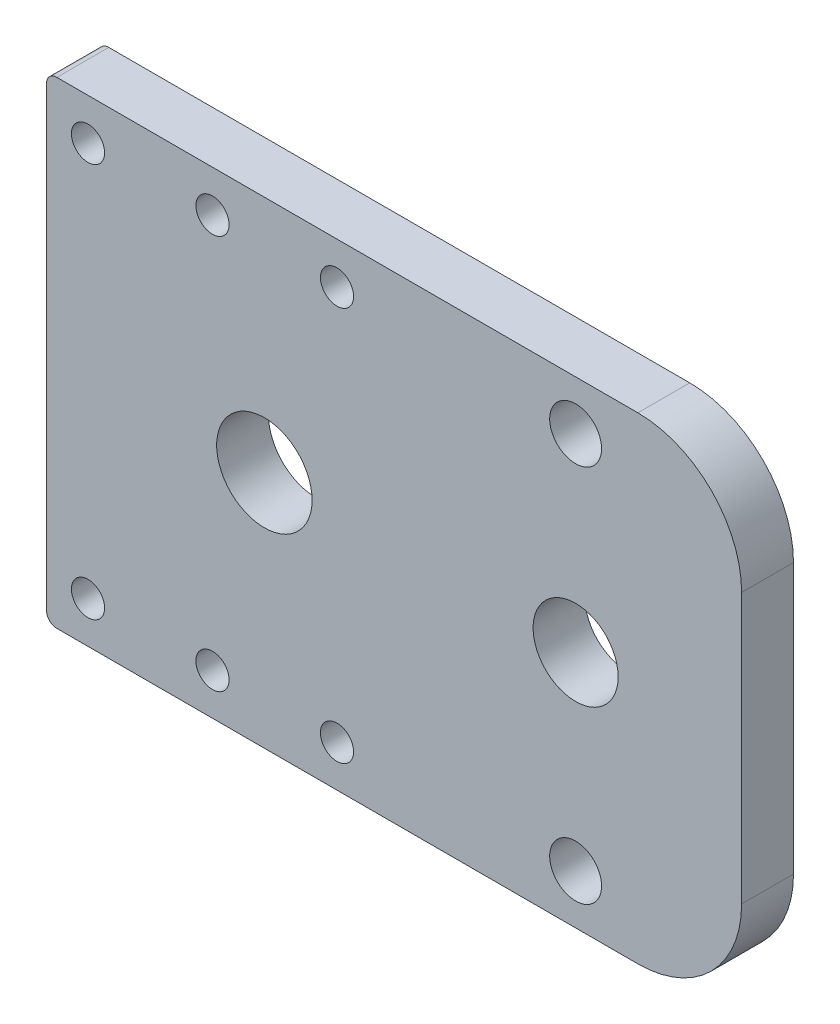
SolidWorks part; units mm, degrees
material "Acrylic (Medium-high impact)"
ref_plane "Front Plane" through (0, 0, 0) normal (0, 0, 1) x (1, 0, 0)
ref_plane "Top Plane" through (0, 0, 0) normal (0, 1, 0) x (1, 0, 0)
ref_plane "Right Plane" through (0, 0, 0) normal (1, 0, 0) x (0, 0, -1)
sketch "Sketch1" plane through (0, 0, 0) normal (0, 0, 1) x (1, 0, 0)
  line L0 (-25.3491, 0) -> (24.7222, 0) construction
  line L1 (40, -23) -> (-40, -23)
  line L2 (40, -23) -> (40, 23)
  line L3 (40, 23) -> (-40, 23)
  line L4 (-40, -23) -> (-40, 23)
  line L5 (40, -23) -> (-40, 23) construction
  line L6 (40, 23) -> (-40, -23) construction
  line L7 (30, 0) -> (30, 18.25)
  line L8 (-40, 23) -> (-25, 23)
  line L9 (-25, 23) -> (-25, -23)
  circle A0 centre (0, 0) radius 4.6
  circle A1 centre (30, 0) radius 4.1
  circle A2 centre (30, 18.25) radius 2.5
  circle A3 centre (30, -18.25) radius 2.5
  point P0 (0, 0)
  dimension "D1" = 9.2
  dimension "D2" = 8.2
  dimension "D7" = 5
  dimension "D3" = 46
  dimension "D4" = 30
  dimension "D5" = 80
  dimension "D6" = 18.25
  dimension "D8" = 15
extrude "Boss-Extrude1" add sketch "Sketch1" along normal blind 5 contours L4 L1 L2 L3 A0 A2 A1 A3 region at (6.9444, 0, 0)
sketch "Sketch2" plane through (0, 0, 5) normal (0, 0, 1) x (1, 0, 0)
  line L0 (-25, -23) -> (-25, 23)
  line L1 (-25, -23) -> (-5, -23)
  line L2 (-25, 23) -> (-5, 23)
  line L3 (-5, -23) -> (-5, 23)
  line L4 (-25, 23) -> (-25, -23)
  line L5 (-25, -23) -> (40, -23)
  line L6 (40, -23) -> (40, 23)
  line L7 (40, 23) -> (-25, 23)
  line L9 (-25, -23) -> (40, -23)
  line L10 (40, -23) -> (40, 23)
  line L11 (40, 23) -> (-25, 23)
  line L12 (-17, 19) -> (-25, 19)
  line L13 (-17, 19) -> (-5, 19)
  line L14 (-5, 19) -> (7, 19)
  line L16 (-5, 0) -> (-25, 0)
  line L20 (-25, 23) -> (-25, -23)
  circle A0 centre (-17, 19) radius 1.6
  circle A1 centre (-5, 19) radius 1.6
  circle A5 centre (7, 19) radius 1.6
  circle A6 centre (7, -19) radius 1.6
  circle A7 centre (-5, -19) radius 1.6
  circle A8 centre (-17, -19) radius 1.6
  dimension "D5" = 3.2
  dimension "D6" = 3.2
  dimension "D7" = 19
  dimension "D8" = 3.2
  dimension "D2" = 20
  dimension "D3" = 12
  dimension "D4" = 12
  dimension "D9" = 8
  dimension "D1" = 0
extrude "Cut-Extrude1" cut sketch "Sketch2" against normal blind 10 contours A8 | A7 L3 | A7 L3 | A6 | A5 | L14 A1 L3 | L3 A1 L13 | L13 A1 L3 | L3 A1 L14 | L13 A0 L12 | L12 A0 L13 region at (7, 20.5547, 5) region at (-5.6791, -19, 5) region at (-4.3209, -19, 5) region at (-17, 19.6791, 5) region at (-17, 18.3209, 5) region at (-5.6791, 18.3209, 5) region at (-4.3209, 18.3209, 5) region at (-5.6791, 19.6791, 5) region at (-4.3209, 19.6791, 5) region at (7, -19, 5) region at (-17, -19, 5)
sketch "Sketch3" plane through (0, 0, 5) normal (0, 0, 1) x (1, 0, 0)
  line L0 (-25, 23) -> (-21, 23)
  line L1 (-21, 23) -> (-21, -23)
  line L4 (40, 23) -> (-25, 23)
  line L5 (-25, 23) -> (-25, -23)
  line L6 (-25, -23) -> (40, -23)
  line L7 (40, -23) -> (40, 23)
  line L8 (40, 23) -> (-25, 23)
  line L9 (-25, 23) -> (-25, -23)
  line L10 (-25, -23) -> (40, -23)
  line L11 (40, -23) -> (40, 23)
  line M10 (40, 23) -> (-25, 23)
  line M11 (-25, 23) -> (-25, -23)
  line M12 (-25, -23) -> (40, -23)
  dimension "D2" = 4
  dimension "D1" = 0
extrude "Cut-Extrude2" cut sketch "Sketch3" against normal through all contours L1 M10 M11 M12 region at (-23, 0, 5)
sketch "Sketch4" plane through (0, 0, 5) normal (0, 0, 1) x (1, 0, 0)
  line L1 (40, 23) -> (46, 23)
  line L2 (40, 23) -> (40, -23)
  line L3 (40, -23) -> (46, -23)
  line L4 (40, 23) -> (-21, 23)
  line L5 (-21, 23) -> (-21, -23)
  line L6 (-21, -23) -> (40, -23)
  line L7 (40, -23) -> (40, 23)
  line L8 (40, 23) -> (-21, 23)
  line L9 (-21, 23) -> (-21, -23)
  line L10 (-21, -23) -> (40, -23)
  line L11 (40, -23) -> (40, 23)
  line L12 (46, 23) -> (46, -23)
  line M19 (40, -23) -> (40, 23)
  dimension "D2" = 6
  dimension "D1" = 0
extrude "Boss-Extrude2" add sketch "Sketch4" against normal up to surface (5 mm away) contours L12 L1 L3 M19 region at (43, 0, 5) up to face at (-15.4, 19, 0)
fillet "Fillet1" radius 10 2 edges at (46, 23, 2.5) (46, -23, 2.5)
fillet "Fillet2" radius 1 2 edges at (-21, 23, 2.5) (-21, -23, 2.5)
